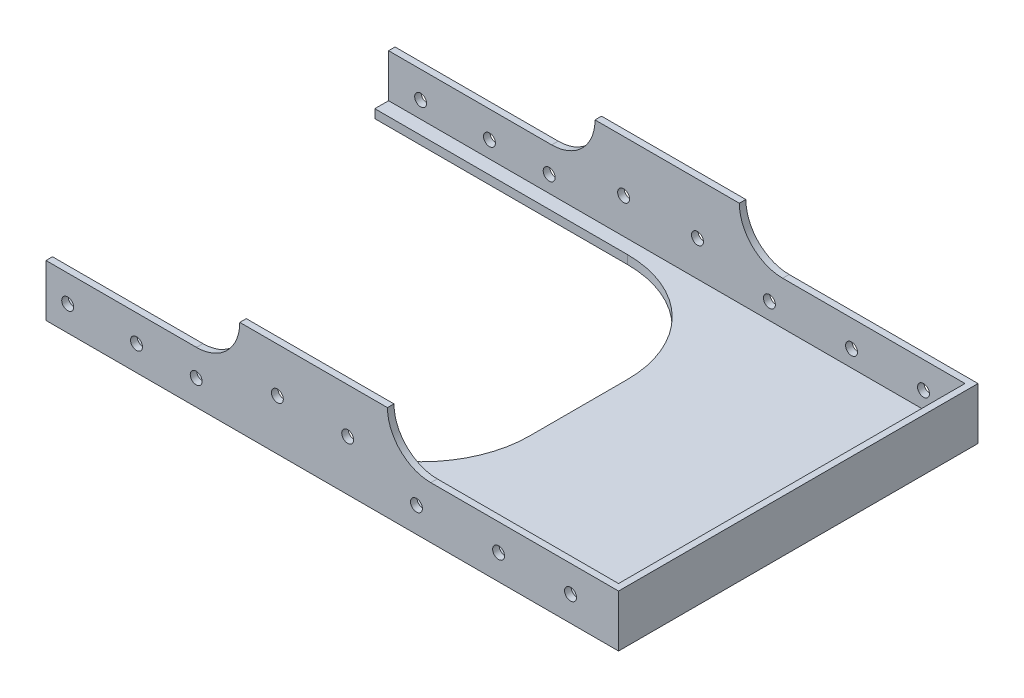
SolidWorks part; units mm, degrees
ref_plane "Front Plane" through (0, 0, 0) normal (0, 0, 1) x (1, 0, 0)
ref_plane "Top Plane" through (0, 0, 0) normal (0, 1, 0) x (1, 0, 0)
ref_plane "Right Plane" through (0, 0, 0) normal (1, 0, 0) x (0, 0, -1)
sketch "Sketch1" plane through (0, 0, 0) normal (0, 1, 0) x (1, 0, 0)
  line L1 (0, 0) -> (278.0499, 0)
  line L2 (0, 0) -> (0, 166.0007)
  line L3 (0, 166.0007) -> (278.0499, 166.0007)
  line L4 (278.0499, 0) -> (278.0499, 166.0007)
extrude "Boss-Extrude1" add sketch "Sketch1" along normal blind 24
sketch "Sketch2" plane through (0, 0, 0) normal (0, -1, 0) x (-1, 0, 0)
  line L1 (-175.4794, 156.6405) -> (14.2402, 156.6405)
  line L2 (-175.4794, 156.6405) -> (-175.4794, 11.5417)
  line L3 (-175.4794, 11.5417) -> (14.2402, 11.5417)
  line L4 (14.2402, 156.6405) -> (14.2402, 11.5417)
extrude "Cut-Extrude1" cut sketch "Sketch2" against normal through all
sketch "Sketch3" plane through (0, 24, 0) normal (0, 1, 0) x (1, 0, 0)
  line L0 (226.9955, 0) -> (226.9955, 3) construction
  line L1 (0, 0) -> (278.0499, 0) construction
  line L2 (278.0499, 166.0007) -> (278.0499, 163.0007) construction
  line L3 (278.0499, 0) -> (278.0499, 166.0007) construction
  line L4 (0, 155.7398) -> (3, 155.7398) construction
  line L5 (0, 166.0007) -> (0, 156.6405) construction
  line L6 (278.0499, 22.4963) -> (275.0499, 22.4963) construction
  line L7 (275.0499, 163.0007) -> (275.0499, 3)
  line L8 (275.0499, 3) -> (3, 3)
  line L9 (3, 3) -> (3, 163.0007)
  line L10 (3, 163.0007) -> (275.0499, 163.0007)
extrude "Cut-Extrude2" cut sketch "Sketch3" against normal blind 20
fillet "Fillet1" radius 50 1 edges at (175.4794, 2, -11.5417) type face fillet first side face at (59.4931, 9.3333, -11.5417) second side face at (175.4794, 2, -84.0911)
fillet "Fillet2" radius 50 1 edges at (175.4794, 2, -156.6405) type face fillet first side face at (175.4794, 2, -109.0911) second side face at (59.4931, 9.3333, -156.6405)
sketch "Sketch4" plane through (0, 24, 0) normal (0, 1, 0) x (1, 0, 0)
  line L0 (0, 0) -> (278.0499, 0) construction
  line L1 (171.3453, 0) -> (103.1403, 0)
  line L2 (171.3453, 0) -> (171.3453, 3)
  line L3 (171.3453, 3) -> (103.1403, 3)
  line L4 (103.1403, 0) -> (103.1403, 3)
  line L5 (3, 3) -> (275.0499, 3) construction
extrude "Boss-Extrude2" add sketch "Sketch4" along normal blind 20
fillet "Fillet4" radius 20 1 edges at (103.1403, 24, -1.5) type face fillet first side face at (103.1403, 34, -1.5) second side face at (35.3801, 24, -4.8472)
fillet "Fillet5" radius 20 1 edges at (171.3453, 24, -1.5) type face fillet first side face at (145.489, 24, -97.7284) second side face at (171.3453, 34, -1.5)
sketch "Sketch5" plane through (0, 24, 0) normal (0, 1, 0) x (1, 0, 0)
  line L0 (278.0499, 166.0007) -> (0, 166.0007) construction
  line L1 (104.1867, 166.0007) -> (170.8443, 166.0007)
  line L2 (104.1867, 166.0007) -> (104.1867, 163.0007)
  line L3 (104.1867, 163.0007) -> (170.8443, 163.0007)
  line L4 (170.8443, 166.0007) -> (170.8443, 163.0007)
  line L5 (275.0499, 163.0007) -> (3, 163.0007) construction
extrude "Boss-Extrude3" add sketch "Sketch5" along normal blind 20
fillet "Fillet6" radius 20 1 edges at (104.1867, 24, -164.5007) type face fillet first side face at (104.1867, 34, -164.5007) second side face at (35.7289, 24, -161.8806)
fillet "Fillet7" radius 20 1 edges at (170.8443, 24, -164.5007) type face fillet first side face at (170.8443, 34, -164.5007) second side face at (228.8223, 24, -83.0003)
sketch "Sketch6" plane through (0, 0, -163.0007) normal (0, 0, 1) x (1, 0, 0)
  circle A0 centre (151.5064, 20.306) radius 2.75
  circle A1 centre (117.3926, 20.306) radius 2.75
extrude "HolesForBolts1" cut sketch "Sketch6" against normal through all
sketch "Sketch7" plane through (0, 0, -166.0007) normal (0, 0, -1) x (-1, 0, 0)
  circle A0 centre (-23.6542, 11.6758) radius 2.75
  circle A1 centre (-55.4415, 11.6758) radius 2.75
  circle A2 centre (-83.0044, 11.6758) radius 2.75
  circle A3 centre (-184.7276, 11.6758) radius 2.75
  circle A4 centre (-222.6455, 11.6758) radius 2.75
  circle A5 centre (-255.8817, 11.6758) radius 2.75
extrude "Cut-Extrude4" cut sketch "Sketch7" against normal through all
sketch "Sketch8" plane through (0, 0, -3) normal (0, 0, -1) x (-1, 0, 0)
  circle A0 centre (-120.4871, 23.2804) radius 2.75
  circle A1 centre (-152.9663, 23.2804) radius 2.75
extrude "Cut-Extrude5" cut sketch "Sketch8" against normal blind 20
ref_plane "Plane1" through (0, 0, -11.5417) normal (0, 0, 1) x (1, 0, 0)
sketch "Sketch11" plane through (0, 0, 0) normal (0, -1, 0) x (1, 0, 0)
  line L0 (125.4794, -11.5417) -> (0, -11.5417) construction
  line L1 (0, 0) -> (13.6461, 0)
  line L2 (0, 0) -> (0, -11.5417)
  line L3 (0, -11.5417) -> (13.6461, -11.5417)
  line L4 (13.6461, 0) -> (13.6461, -11.5417)
extrude "Cut-Extrude6" cut sketch "Sketch11" against normal through all
sketch "Sketch12" plane through (0, 0, 0) normal (0, -1, 0) x (1, 0, 0)
  line L0 (0, -156.6405) -> (125.4794, -156.6405) construction
  line L1 (0, -166.0007) -> (8.8441, -166.0007)
  line L2 (0, -166.0007) -> (0, -156.6405)
  line L3 (0, -156.6405) -> (8.8441, -156.6405)
  line L4 (8.8441, -166.0007) -> (8.8441, -156.6405)
extrude "Cut-Extrude7" cut sketch "Sketch12" against normal through all
